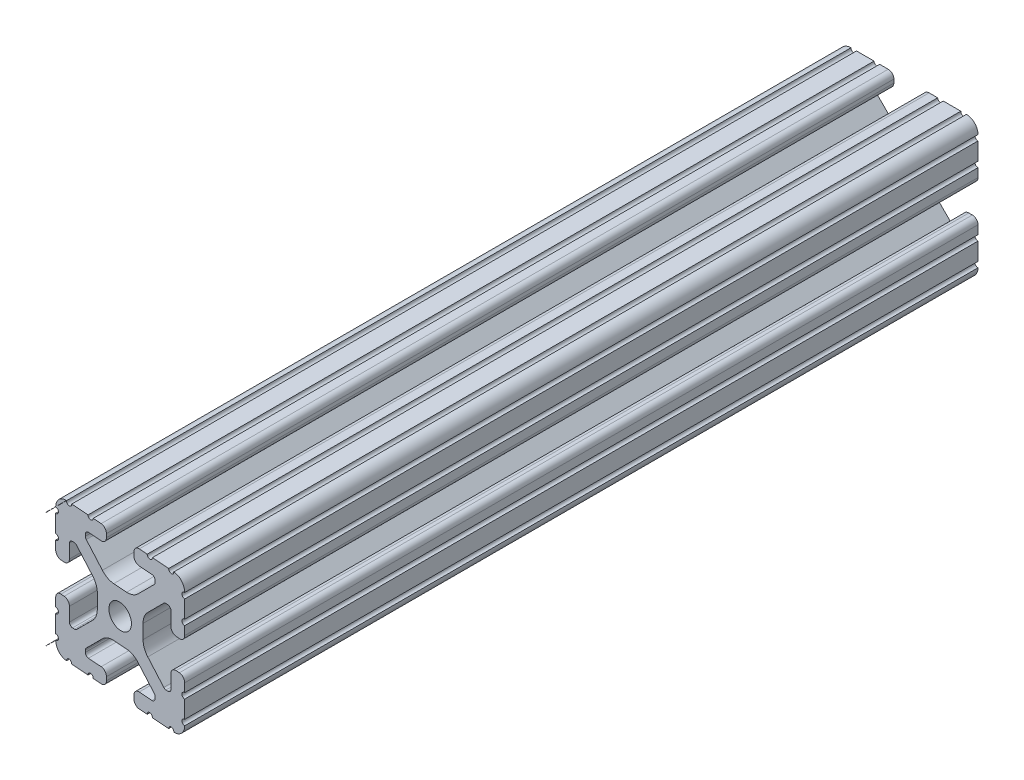
SolidWorks part; units mm, degrees
material "6061 Alloy"
ref_plane "Front Plane" through (0, 0, 0) normal (0, 0, 1) x (1, 0, 0)
ref_plane "Top Plane" through (0, 0, 0) normal (0, 1, 0) x (1, 0, 0)
ref_plane "Right Plane" through (0, 0, 0) normal (1, 0, 0) x (0, 0, -1)
sketch "Sketch1" plane through (0, 0, 0) normal (0, 0, 1) x (1, 0, 0)
  line L0 (0, 25.6181) -> (0, -24.623) construction
  line L1 (-20.8943, 0) -> (20.4607, 0) construction
  line L2 (-10.0229, 12.9148) -> (-5.2522, 8.144)
  line L3 (-10.287, 14.0843) -> (-10.287, 13.5524)
  line L4 (-5.6176, 14.986) -> (-9.3853, 14.986)
  line L5 (-4.064, 17.4964) -> (-4.064, 16.5396)
  line L6 (-7.9742, 19.05) -> (-5.6176, 19.05)
  line L7 (-14.3277, 19.05) -> (-9.4982, 19.05)
  line L8 (-19.05, 9.4961) -> (-19.05, 14.3277)
  line L9 (-19.05, 5.6176) -> (-19.05, 7.9763)
  line L10 (-16.5396, 4.064) -> (-17.4964, 4.064)
  line L11 (-14.986, 9.3853) -> (-14.986, 5.6176)
  line L12 (-13.516, 10.287) -> (-14.0843, 10.287)
  line L13 (-8.1476, 5.2921) -> (-12.8784, 10.0229)
  line L14 (-6.7564, -1.9335) -> (-6.7564, 1.9335)
  line L15 (-12.8784, -10.0229) -> (-8.1476, -5.2921)
  line L16 (-14.0843, -10.287) -> (-13.516, -10.287)
  line L17 (-14.986, -5.6176) -> (-14.986, -9.3853)
  line L18 (-17.4964, -4.064) -> (-16.5396, -4.064)
  line L19 (-19.05, -7.9763) -> (-19.05, -5.6176)
  line L20 (-19.05, -14.3277) -> (-19.05, -9.4961)
  line L21 (-9.4961, -19.05) -> (-14.3277, -19.05)
  line L22 (-5.6176, -19.05) -> (-7.9763, -19.05)
  line L23 (-4.064, -17.4964) -> (-4.064, -16.5396)
  line L24 (10.0229, -12.9148) -> (5.2522, -8.144)
  line L25 (10.287, -14.0843) -> (10.287, -13.5524)
  line L26 (5.6176, -14.986) -> (9.3853, -14.986)
  line L28 (-1.9022, 6.7564) -> (1.9022, 6.7564)
  line L29 (-1.9022, -6.7564) -> (1.9022, -6.7564)
  line L31 (-5.6176, -14.986) -> (-9.3853, -14.986)
  line L32 (-10.287, -14.0843) -> (-10.287, -13.5524)
  line L33 (-10.0229, -12.9148) -> (-5.2522, -8.144)
  line L66 (4.064, -16.5396) -> (4.064, -17.4964)
  line L67 (5.6176, -19.05) -> (7.9763, -19.05)
  line L68 (9.4961, -19.05) -> (14.3277, -19.05)
  line L69 (19.05, -14.3277) -> (19.05, -9.4961)
  line L70 (19.05, -7.9763) -> (19.05, -5.6176)
  line L71 (17.4964, -4.064) -> (16.5396, -4.064)
  line L72 (14.986, -5.6176) -> (14.986, -9.3853)
  line L73 (14.0843, -10.287) -> (13.516, -10.287)
  line L74 (12.8784, -10.0229) -> (8.1476, -5.2921)
  line L75 (6.7564, -1.9335) -> (6.7564, 1.9335)
  line L76 (8.1476, 5.2921) -> (12.8784, 10.0229)
  line L77 (13.516, 10.287) -> (14.0843, 10.287)
  line L78 (14.986, 9.3853) -> (14.986, 5.6176)
  line L79 (16.5396, 4.064) -> (17.4964, 4.064)
  line L80 (19.05, 5.6176) -> (19.05, 7.9763)
  line L81 (19.05, 9.4961) -> (19.05, 14.3277)
  line L82 (14.3277, 19.05) -> (9.4982, 19.05)
  line L83 (7.9742, 19.05) -> (5.6176, 19.05)
  line L84 (4.064, 17.4964) -> (4.064, 16.5396)
  line L85 (5.6176, 14.986) -> (9.3853, 14.986)
  line L86 (10.287, 14.0843) -> (10.287, 13.5524)
  line L87 (10.0229, 12.9148) -> (5.2522, 8.144)
  arc A0 (-10.0229, 12.9148) -> (-10.287, 13.5524) centre (-9.3853, 13.5524) cw
  circle A1 centre (0, 0) radius 3.3274
  arc A2 (-10.287, 14.0843) -> (-9.3853, 14.986) centre (-9.3853, 14.0843) cw
  arc A3 (-4.064, 16.5396) -> (-5.6176, 14.986) centre (-5.6176, 16.5396) cw
  arc A4 (-5.6176, 19.05) -> (-4.064, 17.4964) centre (-5.6176, 17.4964) cw
  arc A5 (-7.9742, 19.05) -> (-9.4982, 19.05) centre (-8.7362, 19.05) cw
  arc A6 (-14.3277, 19.05) -> (-15.8475, 19.05) centre (-15.0876, 18.9933) cw
  arc A7 (-19.05, 15.8475) -> (-15.8475, 19.05) centre (-15.8751, 15.8751) cw
  arc A8 (-19.05, 15.8475) -> (-19.05, 14.3277) centre (-18.9933, 15.0876) cw
  arc A9 (-19.05, 9.4961) -> (-19.05, 7.9763) centre (-18.9933, 8.7362) cw
  arc A10 (-17.4964, 4.064) -> (-19.05, 5.6176) centre (-17.4964, 5.6176) cw
  arc A11 (-14.986, 5.6176) -> (-16.5396, 4.064) centre (-16.5396, 5.6176) cw
  arc A12 (-14.986, 9.3853) -> (-14.0843, 10.287) centre (-14.0843, 9.3853) cw
  arc A13 (-13.516, 10.287) -> (-12.8784, 10.0229) centre (-13.516, 9.3853) cw
  arc A14 (-8.1476, 5.2921) -> (-6.7564, 1.9335) centre (-11.5062, 1.9335) cw
  arc A15 (-6.7564, -1.9335) -> (-8.1476, -5.2921) centre (-11.5062, -1.9335) cw
  arc A16 (-12.8784, -10.0229) -> (-13.516, -10.287) centre (-13.516, -9.3853) cw
  arc A17 (-14.0843, -10.287) -> (-14.986, -9.3853) centre (-14.0843, -9.3853) cw
  arc A18 (-16.5396, -4.064) -> (-14.986, -5.6176) centre (-16.5396, -5.6176) cw
  arc A19 (-19.05, -5.6176) -> (-17.4964, -4.064) centre (-17.4964, -5.6176) cw
  arc A20 (-19.05, -7.9763) -> (-19.05, -9.4961) centre (-18.9933, -8.7362) cw
  arc A21 (-19.05, -14.3277) -> (-19.05, -15.8475) centre (-18.9933, -15.0876) cw
  arc A22 (-15.8475, -19.05) -> (-19.05, -15.8475) centre (-15.8751, -15.8751) cw
  arc A23 (-15.8475, -19.05) -> (-14.3277, -19.05) centre (-15.0876, -18.9933) cw
  arc A24 (-9.4961, -19.05) -> (-7.9763, -19.05) centre (-8.7362, -18.9933) cw
  arc A25 (-4.064, -17.4964) -> (-5.6176, -19.05) centre (-5.6176, -17.4964) cw
  arc A26 (-5.2522, -8.144) -> (-1.9022, -6.7564) centre (-1.9022, -11.494) cw
  arc A27 (1.9022, -6.7564) -> (5.2522, -8.144) centre (1.9022, -11.494) cw
  arc A28 (10.0229, -12.9148) -> (10.287, -13.5524) centre (9.3853, -13.5524) cw
  arc A29 (10.287, -14.0843) -> (9.3853, -14.986) centre (9.3853, -14.0843) cw
  arc A30 (4.064, -16.5396) -> (5.6176, -14.986) centre (5.6176, -16.5396) cw
  arc A31 (-4.064, -16.5396) -> (-5.6176, -14.986) centre (-5.6176, -16.5396) ccw
  arc A32 (-10.287, -14.0843) -> (-9.3853, -14.986) centre (-9.3853, -14.0843) ccw
  arc A33 (-10.0229, -12.9148) -> (-10.287, -13.5524) centre (-9.3853, -13.5524) ccw
  arc A79 (4.064, -17.4964) -> (5.6176, -19.05) centre (5.6176, -17.4964) ccw
  arc A80 (9.4961, -19.05) -> (7.9763, -19.05) centre (8.7362, -18.9933) ccw
  arc A81 (15.8475, -19.05) -> (14.3277, -19.05) centre (15.0876, -18.9933) ccw
  arc A82 (15.8475, -19.05) -> (19.05, -15.8475) centre (15.8751, -15.8751) ccw
  arc A83 (19.05, -14.3277) -> (19.05, -15.8475) centre (18.9933, -15.0876) ccw
  arc A84 (19.05, -7.9763) -> (19.05, -9.4961) centre (18.9933, -8.7362) ccw
  arc A85 (19.05, -5.6176) -> (17.4964, -4.064) centre (17.4964, -5.6176) ccw
  arc A86 (16.5396, -4.064) -> (14.986, -5.6176) centre (16.5396, -5.6176) ccw
  arc A87 (14.0843, -10.287) -> (14.986, -9.3853) centre (14.0843, -9.3853) ccw
  arc A88 (12.8784, -10.0229) -> (13.516, -10.287) centre (13.516, -9.3853) ccw
  arc A89 (6.7564, -1.9335) -> (8.1476, -5.2921) centre (11.5062, -1.9335) ccw
  arc A90 (8.1476, 5.2921) -> (6.7564, 1.9335) centre (11.5062, 1.9335) ccw
  arc A91 (13.516, 10.287) -> (12.8784, 10.0229) centre (13.516, 9.3853) ccw
  arc A92 (14.986, 9.3853) -> (14.0843, 10.287) centre (14.0843, 9.3853) ccw
  arc A93 (14.986, 5.6176) -> (16.5396, 4.064) centre (16.5396, 5.6176) ccw
  arc A94 (17.4964, 4.064) -> (19.05, 5.6176) centre (17.4964, 5.6176) ccw
  arc A95 (19.05, 9.4961) -> (19.05, 7.9763) centre (18.9933, 8.7362) ccw
  arc A96 (19.05, 15.8475) -> (19.05, 14.3277) centre (18.9933, 15.0876) ccw
  arc A97 (19.05, 15.8475) -> (15.8475, 19.05) centre (15.8751, 15.8751) ccw
  arc A98 (14.3277, 19.05) -> (15.8475, 19.05) centre (15.0876, 18.9933) ccw
  arc A99 (7.9742, 19.05) -> (9.4982, 19.05) centre (8.7362, 19.05) ccw
  arc A100 (5.6176, 19.05) -> (4.064, 17.4964) centre (5.6176, 17.4964) ccw
  arc A101 (4.064, 16.5396) -> (5.6176, 14.986) centre (5.6176, 16.5396) ccw
  arc A102 (10.287, 14.0843) -> (9.3853, 14.986) centre (9.3853, 14.0843) ccw
  arc A103 (10.0229, 12.9148) -> (10.287, 13.5524) centre (9.3853, 13.5524) ccw
  arc A104 (1.9022, 6.7564) -> (5.2522, 8.144) centre (1.9022, 11.494) ccw
  arc A105 (-5.2522, 8.144) -> (-1.9022, 6.7564) centre (-1.9022, 11.494) ccw
  dimension "D1" = 6.6548
  dimension "D2" = 19.05
  dimension "D3" = 38.1
  dimension "D4" = 20.574
  dimension "D5" = 13.5128
  dimension "D6" = 4.064
  dimension "D7" = 8.128
  dimension "D8" = 4.064
  dimension "D9" = 12.2936
extrude "Extrude1" add sketch "Sketch1" against normal blind 217.932
sketch "Sketch2" plane through (0, 19.05, 0) normal (0, 1, 0) x (1, 0, 0)
  line L0 (19.05, 0) -> (-19.05, 2.6642)
  line L1 (-19.05, 217.932) -> (-19.05, 0) construction
  line L2 (-19.05, 2.6642) -> (-19.05, 0)
  line L3 (-19.05, 0) -> (19.05, 0)
  dimension "D1" = 4
extrude "Cut-Extrude1" cut sketch "Sketch2" against normal offset from surface (127 mm away) 127 up to face at (-11.9129, 19.05, -108.966)
